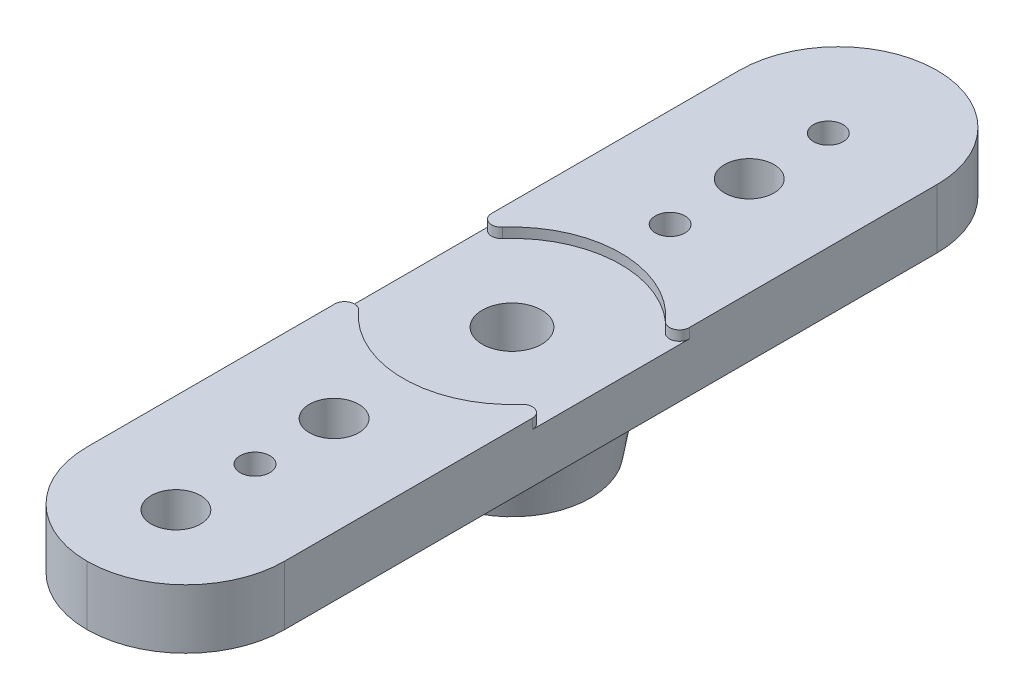
SolidWorks part; units mm, degrees
ref_plane "Front Plane" through (0, 0, 0) normal (0, 0, 1) x (1, 0, 0)
ref_plane "Top Plane" through (0, 0, 0) normal (0, 1, 0) x (1, 0, 0)
ref_plane "Right Plane" through (0, 0, 0) normal (1, 0, 0) x (0, 0, -1)
sketch "Sketch1" plane through (0, 0, 0) normal (0, 1, 0) x (1, 0, 0)
  line L1 (-5, 21.5) -> (5, 21.5)
  line L2 (-5, 21.5) -> (-5, -21.5)
  line L3 (-5, -21.5) -> (5, -21.5)
  line L4 (5, 21.5) -> (5, -21.5)
  point P4 (0, 21.5)
  point P6 (5, 0)
  dimension "D1" = 10
  dimension "D2" = 43
extrude "Boss-Extrude1" add sketch "Sketch1" along normal blind 3
fillet "Fillet1" radius 5 4 edges at (-5, 1.5, -21.5) (5, 1.5, -21.5) (5, 1.5, 21.5) (-5, 1.5, 21.5)
sketch "Sketch2" plane through (0, 0, 0) normal (0, 1, 0) x (1, 0, 0)
  circle A0 centre (0, 0) radius 4.5
  dimension "D1" = 9
extrude "Boss-Extrude2" add sketch "Sketch2" against normal blind 3
draft "Draft1" type of draft neutral plane draft angle 10 faces to draft 1 face at (0, -3, 4.5) neutral plane through (0, 0, 0) neutral plane normal (0, -1, 0) parameters "D1"=10
sketch "Sketch3" plane through (0, -3, 0) normal (0, -1, 0) x (1, 0, 0)
  circle A0 centre (0, 0) radius 3
  dimension "D1" = 6
extrude "Cut-Extrude1" cut sketch "Sketch3" against normal blind 3
sketch "Sketch4" plane through (0, 0, 0) normal (0, -1, 0) x (1, 0, 0)
  circle A0 centre (0, 0) radius 1.5
  dimension "D1" = 3
extrude "Cut-Extrude2" cut sketch "Sketch4" against normal through all
sketch "Sketch5" plane through (0, 3, 0) normal (0, 1, 0) x (1, 0, 0)
  circle A0 centre (0, 0) radius 5.5
  dimension "D1" = 11
extrude "Cut-Extrude3" cut sketch "Sketch5" against normal blind 0.5
fillet "Fillet2" radius 0.5 4 edges at (5, 2.75, 2.2913) (-5, 2.75, 2.2913) (5, 2.75, -2.2913) (-5, 2.75, -2.2913)
sketch "Sketch6" plane through (0, 3, 0) normal (0, 1, 0) x (1, 0, 0)
  line L0 (0, 8) -> (0, 16) construction
  line L1 (0, -17) -> (0, -9) construction
  circle A0 centre (0, 12) radius 1.25
  circle A1 centre (0, 16) radius 0.75
  circle A2 centre (0, 8) radius 0.75
  circle A3 centre (0, -17) radius 1.25
  circle A4 centre (0, -9) radius 1.25
  circle A5 centre (0, -13) radius 0.75
  point P7 (0, 0)
  dimension "D1" = 2.5
  dimension "D2" = 1.5
  dimension "D3" = 8
  dimension "D4" = 12
  dimension "D5" = 13
extrude "Cut-Extrude4" cut sketch "Sketch6" against normal through all
